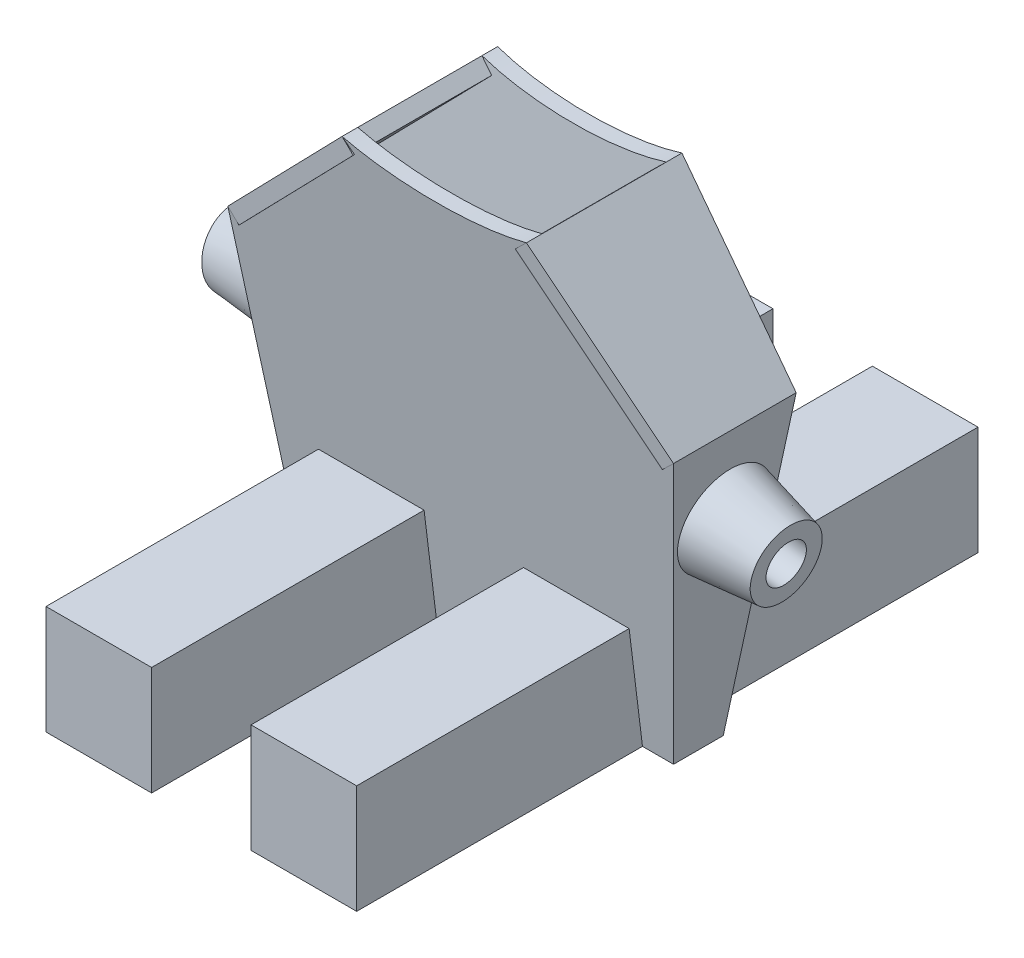
SolidWorks part; units mm, degrees
ref_plane "Front" through (0, 0, 0) normal (0, 0, 1) x (1, 0, 0)
ref_plane "Top" through (0, 0, 0) normal (0, 1, 0) x (1, 0, 0)
ref_plane "Right" through (0, 0, 0) normal (1, 0, 0) x (0, 0, -1)
sketch "Sketch1" plane through (0, 0, 0) normal (0, 1, 0) x (1, 0, 0)
  line L1 (-6, 0.8) -> (6, 0.8)
  line L2 (-6, 0.8) -> (-6, -0.8)
  line L3 (-6, -0.8) -> (6, -0.8)
  line L4 (6, 0.8) -> (6, -0.8)
  line L5 (-6, 0.8) -> (6, -0.8) construction
  line L6 (-6, -0.8) -> (6, 0.8) construction
  point P0 (0, 0)
  dimension "D1" = 1.6
  dimension "D2" = 12
extrude "Boss-Extrude1" add sketch "Sketch1" along normal blind 15 draft 7 draft outward yes
shell "Shell1" thickness 0.5 removed face at (0, 15, 0)
sketch "Sketch6" plane through (0, 0, 0) normal (0, -1, 0) x (1, 0, 0)
  line L1 (-1.6, -10) -> (-5, -10)
  line L2 (-1.6, -10) -> (-1.6, 10)
  line L3 (-1.6, 10) -> (-5, 10)
  line L4 (-5, -10) -> (-5, 10)
  line L5 (-1.6, -10) -> (-5, 10) construction
  line L6 (-1.6, 10) -> (-5, -10) construction
  line L7 (1.6, 10) -> (5, 10)
  line L8 (1.6, 10) -> (1.6, -10)
  line L9 (1.6, -10) -> (5, -10)
  line L10 (5, 10) -> (5, -10)
  line L11 (1.6, 10) -> (5, -10) construction
  line L12 (1.6, -10) -> (5, 10) construction
  point P0 (-3.3, 0)
  point P5 (3.3, 0)
  dimension "D1" = 3.4
  dimension "D2" = 20
  dimension "D3" = 3.4
extrude "Boss-Extrude2" add sketch "Sketch6" against normal blind 3.5 separate body
sketch "Sketch11" plane through (0, 0, 0) normal (0, 0, 1) x (1, 0, 0)
  line L1 (-7.8418, 15) -> (7.8418, 15) construction
  ellipse E0 centre (0, 15) end of major axis (4.5, 15) minor radius 1.5
extrude "Cut-Extrude11" cut sketch "Sketch11" against normal blind 10 and the other way blind 10
sketch "Sketch18" plane through (0, 0, 0) normal (0, 0, 1) x (1, 0, 0)
  line L0 (-2.9665, 13.8721) -> (-7.1737, 9.559)
  line L1 (-7.8418, 15) -> (-6, 0) construction
  line L2 (-7.1737, 9.559) -> (-8.985, 15.8134)
  line L3 (-8.985, 15.8134) -> (-2.9665, 15.8134)
  line L4 (-2.9665, 15.8134) -> (-2.9665, 13.8721)
extrude "Cut-Extrude12" cut sketch "Sketch18" against normal blind 10 and the other way blind 10
sketch "Sketch19" plane through (-8.454, 8.2465, 0) normal (-0.7158, 0.6983, 0) x (0, 0, 1)
  line L0 (1.9737, 1.8336) -> (2.5033, 7.8588)
  line L1 (2.5033, 7.8588) -> (-2.5033, 7.8588)
  line L2 (1.9737, 1.8336) -> (-1.9737, 1.8336)
  line L3 (-1.9737, 1.8336) -> (-2.5033, 7.8588)
extrude "Boss-Extrude3" add sketch "Sketch19" against normal blind 0.5
mirror "Mirror3" about plane through (0, 0, 0) normal (1, 0, 0) of "Boss-Extrude3"
sketch "Sketch30" plane through (0, 0, 0) normal (0, -1, 0) x (1, 0, 0)
  line L0 (1.6, 10) -> (1.6, -10) construction
  line L1 (-1.6, 0.8) -> (1.6, 0.8)
  line L2 (-1.6, 0.8) -> (-1.6, -0.8)
  line L3 (-1.6, -0.8) -> (1.6, -0.8)
  line L4 (1.6, 0.8) -> (1.6, -0.8)
  line L5 (-1.6, 0.8) -> (1.6, -0.8) construction
  line L6 (-1.6, -0.8) -> (1.6, 0.8) construction
  line L7 (6, -0.8) -> (-6, -0.8) construction
  point P0 (0, 0)
extrude "Boss-Extrude6" add sketch "Sketch30" against normal blind 9 draft 6 draft outward yes
mirror "Mirror7" about plane through (0, 0, 0) normal (1, 0, 0) of "Cut-Extrude12"
sketch "Sketch31" plane through (5.9109, -0.7258, 0) normal (0.9925, -0.1219, 0) x (0, 0, -1)
  circle A0 centre (0, 7.633) radius 1.5046
extrude "Boss-Extrude7" add sketch "Sketch31" along normal blind 2 draft 10
mirror "Mirror8" about plane through (0, 0, 0) normal (1, 0, 0) of "Boss-Extrude7"
sketch "Sketch32" plane through (7.896, -0.9695, 0) normal (0.9925, -0.1219, 0) x (0, 0, -1)
  circle A0 centre (0, 7.633) radius 0.6455
extrude "Cut-Extrude13" cut sketch "Sketch32" against normal blind 4
mirror "Mirror9" about plane through (0, 0, 0) normal (1, 0, 0) of "Cut-Extrude13"
